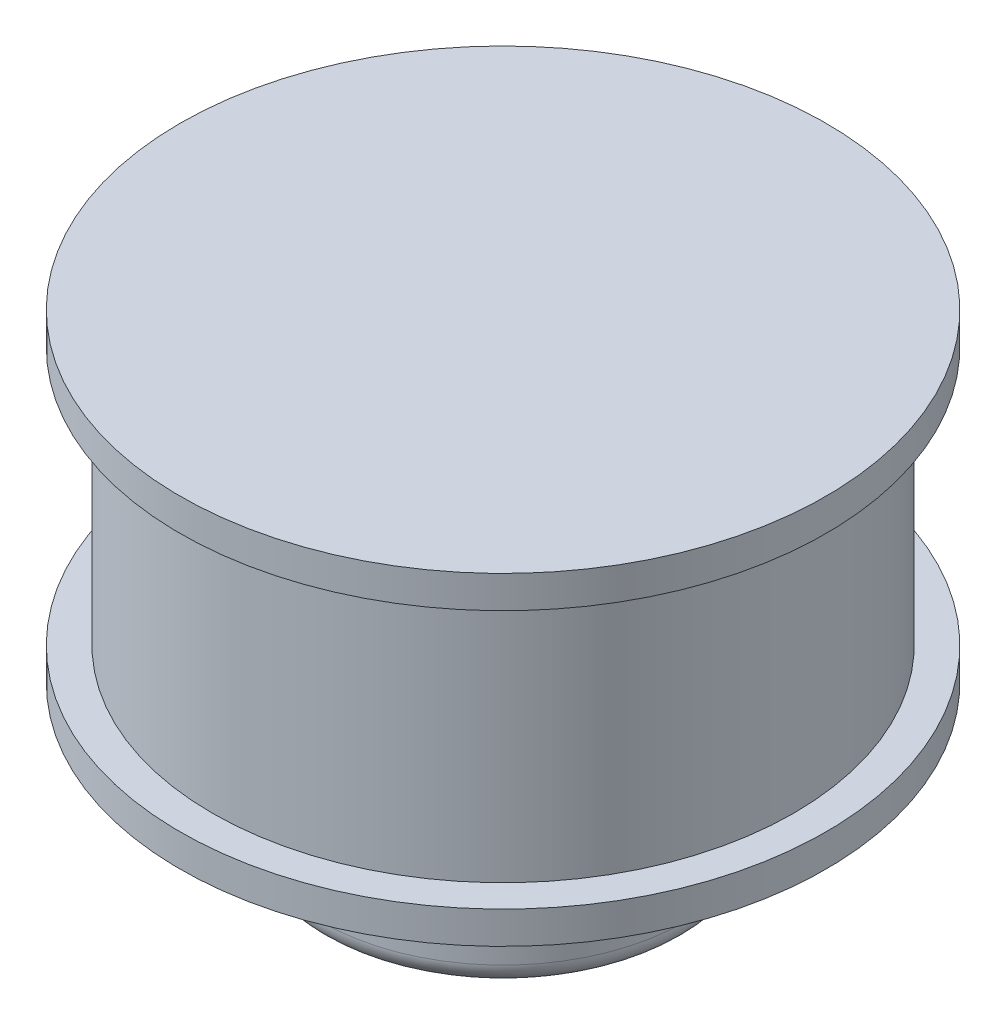
SolidWorks part; units mm, degrees
material "ABS"
ref_plane "Front Plane" through (0, 0, 0) normal (0, 0, 1) x (1, 0, 0)
ref_plane "Top Plane" through (0, 0, 0) normal (0, 1, 0) x (1, 0, 0)
ref_plane "Right Plane" through (0, 0, 0) normal (1, 0, 0) x (0, 0, -1)
sketch "Sketch1" plane through (0, 0, 0) normal (0, 0, 1) x (1, 0, 0)
  line L2 (-8.5, -6.35) -> (-8.5, 0)
  line L3 (-8.5, 0) -> (-15, 0)
  line L4 (-15, 0) -> (-15, 1.5)
  line L5 (-15, 1.5) -> (-13.5, 1.5)
  line L6 (-13.5, 1.5) -> (-13.5, 13.5)
  line L7 (-13.5, 13.5) -> (-15, 13.5)
  line L8 (-15, 13.5) -> (-15, 15)
  line L9 (-15, 15) -> (0, 15)
  line L10 (0, 15) -> (0, 7.65)
  line L11 (-4, -6.35) -> (-8.5, -6.35)
  line L12 (-4, 7.65) -> (-4, -6.35)
  line L13 (0, 7.65) -> (-4, 7.65)
  dimension "D1" = 8.5
  dimension "D2" = 1.5
  dimension "D3" = 6.35
  dimension "D4" = 1.5
  dimension "D5" = 4
  dimension "D6" = 14
  dimension "D7" = 15
  dimension "D8" = 15
revolve "Revolve1" add sketch "Sketch1" angle 360 about L10
fillet "Fillet1" radius 1 2 edges at (-8.5, -6.35, 0) (-4, -6.35, 0)
hole_wizard "M2x0.4 Tapped Hole1" positions "Sketch2" profile "Sketch3" tap size "M2x0.4" standard "ANSI Metric" end condition up to next
sketch "Sketch2" plane through (0, 0, 0) normal (0, 0, 1) x (1, 0, 0)
  line L0 (-7.5, -6.35) -> (7.5, -6.35) construction
  point P0 (0, -2.35)
  dimension "D1" = 4
sketch "Sketch3" plane through (0, -2.35, 0) normal (1, 0, 0) x (0, 1, 0)
  line L0 (0, 0) -> (0, 8.5)
  line L1 (0, 8.5) -> (0.8, 8.5)
  line L2 (0.8, 8.5) -> (0.8, 0)
  line L5 (0.8, 0) -> (0, 0)
  line L11 (0, -6.35) -> (0, 107.95) construction
  dimension "Thru Tap Drill Dia." = 1.6
  dimension "Thru Tap Drill Depth" = 8.5
cosmetic thread "Hole Thread1" parameters "D2"=2
